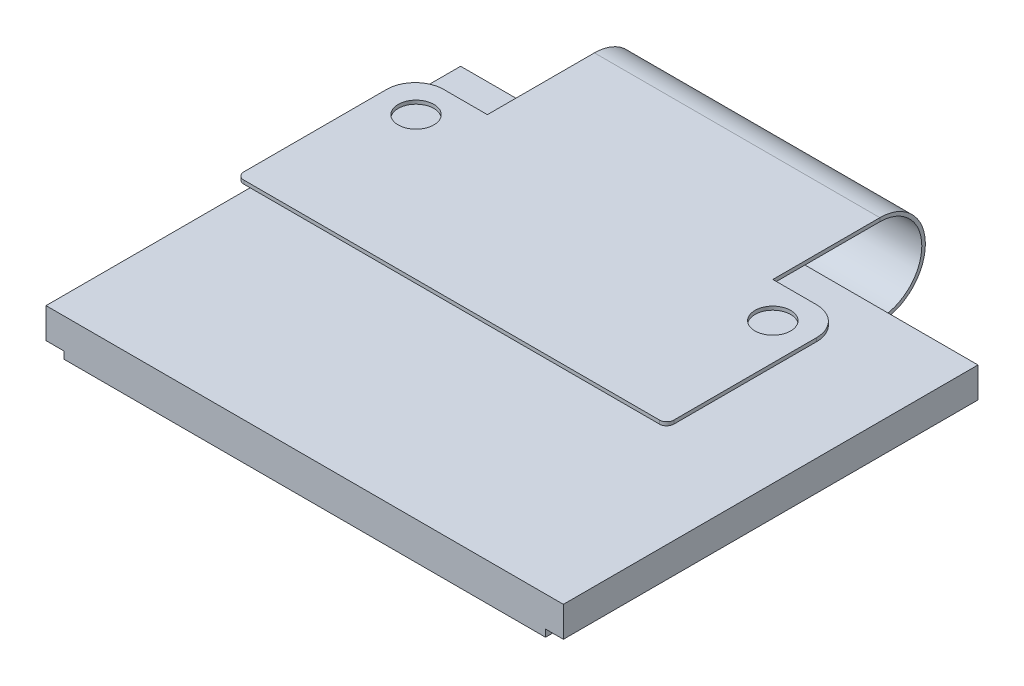
SolidWorks part; units mm, degrees
ref_plane "Front Plane" through (0, 0, 0) normal (0, 0, 1) x (1, 0, 0)
ref_plane "Top Plane" through (0, 0, 0) normal (0, 1, 0) x (1, 0, 0)
ref_plane "Right Plane" through (0, 0, 0) normal (1, 0, 0) x (0, 0, -1)
sketch "Sketch2" plane through (0, 0, 0) normal (0, 1, 0) x (1, 0, 0)
  line L1 (-7.25, 5.81) -> (7.25, 5.81)
  line L2 (-7.25, 5.81) -> (-7.25, -5.81)
  line L3 (-7.25, -5.81) -> (7.25, -5.81)
  line L4 (7.25, 5.81) -> (7.25, -5.81)
  line L5 (-7.25, 5.81) -> (7.25, -5.81) construction
  line L6 (-7.25, -5.81) -> (7.25, 5.81) construction
  point P0 (0, 0)
extrude "Boss-Extrude1" add sketch "Sketch2" along normal mid plane 0.85
sketch "Sketch6" plane through (0, -0.425, 0) normal (0, -1, 0) x (1, 0, 0)
  line L0 (-7.25, 5.81) -> (7.25, 5.81) construction
  line L1 (-6.75, 5.81) -> (6.75, 5.81)
  line L2 (-6.75, 5.81) -> (-6.75, -2.29)
  line L3 (-6.75, -2.29) -> (6.75, -2.29)
  line L4 (6.75, 5.81) -> (6.75, -2.29)
  line L5 (-6.75, 5.81) -> (6.75, -2.29) construction
  line L6 (-6.75, -2.29) -> (6.75, 5.81) construction
  point P0 (0, 1.76)
  dimension "D1" = 0
  dimension "D2" = 0
  dimension "D3" = 8.1
  dimension "D4" = 13.5
extrude "Boss-Extrude2" add sketch "Sketch6" along normal blind 0.2
sketch "Sketch9" plane through (0, -0.425, 0) normal (0, -1, 0) x (1, 0, 0)
  line L1 (-6.096, -2.4527) -> (6.096, -2.4527)
  line L2 (-6.096, -2.4527) -> (-6.096, -4.9927)
  line L3 (-6.096, -4.9927) -> (-3.2893, -4.9927)
  line L4 (6.096, -2.4527) -> (6.096, -4.9927)
  line L5 (-6.096, -2.4527) -> (6.096, -4.9927) construction
  line L6 (-6.096, -4.9927) -> (6.096, -2.4527) construction
  line L7 (-6.75, -2.29) -> (6.75, -2.29) construction
  line L8 (-3.2893, -7.8563) -> (3.2893, -7.8563)
  line L9 (-3.2893, -4.9927) -> (-3.2893, -7.8563)
  line L10 (0, 0) -> (0, -4.9927) construction
  line L11 (3.2893, -4.9927) -> (3.2893, -7.8563)
  line L12 (3.2893, -4.9927) -> (6.096, -4.9927)
  line L13 (0, -7.8563) -> (0, -11.701) construction
  point P0 (0, -3.7227)
  point P11 (0, -7.8563)
  dimension "D1" = 0.1627
  dimension "D2" = 12.192
  dimension "D3" = 0
  dimension "D4" = 2.54
  dimension "D5" = 2.8636
  dimension "D6" = 6.5786
extrude "Boss-Extrude4" add sketch "Sketch9" along normal blind 0.1755
fillet "Fillet1" radius 0.762 2 edges at (6.096, -0.5127, -4.9927) (-6.096, -0.5127, -4.9927)
fillet "Fillet2" radius 0.2 2 edges at (3.2893, -0.5127, -7.8563) (-3.2893, -0.5127, -7.8563)
sketch "Sketch12" plane through (0, 0, 0) normal (1, 0, 0) x (0, 0, -1)
  line L0 (5.81, -0.425) -> (6.31, -0.425)
  line L2 (6.31, 2.125) -> (-1.69, 2.125)
  arc A1 (6.31, -0.425) -> (6.31, 2.125) centre (6.31, 0.85) ccw
  point P3 (7.585, 0.85)
  point P7 (6.31, 2.125)
  dimension "D2" = 2.55
  dimension "D3" = 8
  dimension "D1" = 0.5
sketch "Sketch13" plane through (0, 0, -5.81) normal (0, 0, -1) x (-1, 0, 0)
  line L0 (-3.2893, -0.425) -> (3.2893, -0.425) construction
  line L2 (-4, -0.425) -> (-4, -0.325)
  line L3 (-4, -0.325) -> (4, -0.325)
  line L4 (4, -0.425) -> (4, -0.325)
  line L5 (0, -0.425) -> (4, -0.325) construction
  line L6 (-4, -0.325) -> (0, -0.425) construction
  line L7 (-4, -0.425) -> (4, -0.425)
  point P0 (0, -0.425)
  dimension "D1" = 0.1
  dimension "D2" = 0
  dimension "D3" = 8
  dimension "D4" = 4
sweep "Sweep2" add profiles "Sketch13" path "Sketch12"
sketch "Sketch14" plane through (0, 2.125, 0) normal (0, 1, 0) x (1, 0, 0)
  line L1 (-4, -1.69) -> (-6.0249, -1.69)
  line L2 (-4, -1.69) -> (-4, 3.31)
  line L3 (-4, 3.31) -> (-6.0249, 3.31)
  line L4 (-6.0249, -1.69) -> (-6.0249, 3.31)
  line L5 (4, -1.69) -> (6.0249, -1.69)
  line L6 (4, -1.69) -> (4, 3.31)
  line L7 (4, 3.31) -> (6.0249, 3.31)
  line L8 (6.0249, -1.69) -> (6.0249, 3.31)
extrude "Boss-Extrude6" add sketch "Sketch14" against normal blind 0.1
sketch "Sketch17" plane through (0, 2.125, 0) normal (0, 1, 0) x (1, 0, 0)
  line L0 (6.0249, -1.69) -> (-6.0249, -1.69) construction
  circle A0 centre (-5, 2.31) radius 0.5
  circle A1 centre (5, 2.31) radius 0.5
  dimension "D3" = 1
  dimension "D4" = 1
  dimension "D1" = 5
  dimension "D2" = 5
  dimension "D5" = 4
  dimension "D6" = 4
extrude "Cut-Extrude3" cut sketch "Sketch17" against normal blind 0.1
fillet "Fillet3" radius 0.2 2 edges at (6.0249, 2.075, 1.69) (-6.0249, 2.075, 1.69)
fillet "Fillet4" radius 0.8 2 edges at (6.0249, 2.075, -3.31) (-6.0249, 2.075, -3.31)
